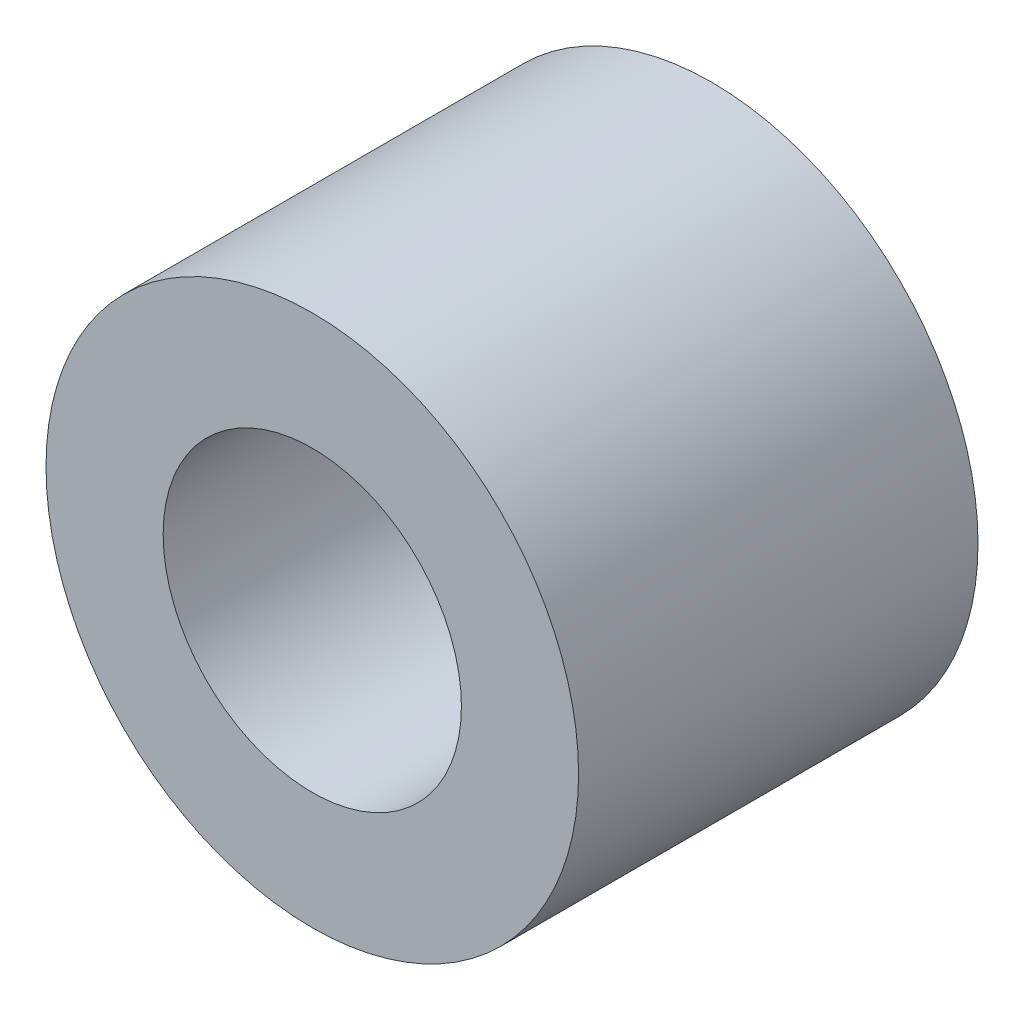
SolidWorks part; units mm, degrees
ref_plane "Front Plane" through (0, 0, 0) normal (0, 0, 1) x (1, 0, 0)
ref_plane "Top Plane" through (0, 0, 0) normal (0, 1, 0) x (1, 0, 0)
ref_plane "Right Plane" through (0, 0, 0) normal (1, 0, 0) x (0, 0, -1)
sketch "Sketch1" plane through (0, 0, 0) normal (0, 0, 1) x (1, 0, 0)
  circle A0 centre (0, 0) radius 3.175
  circle A1 centre (0, 0) radius 1.778
  dimension "OD" = 6.35
  dimension "ID" = 3.556
extrude "Extrude1" add sketch "Sketch1" along normal mid plane 4.7625
sketch "Sketch2" plane through (0, 0, 0) normal (1, 0, 0) x (0, 0, -1)
  line L0 (-2.3813, -1.778) -> (2.3812, -1.778) construction
  line L3 (2.3812, 1.778) -> (-2.3813, 1.778) construction
  line L5 (-2.3813, -1.778) -> (2.3812, -1.778)
  line L6 (2.3812, 1.778) -> (-2.3813, 1.778)
sketch "Sketch4" plane through (0, 0, 2.3813) normal (0, 0, 1) x (1, 0, 0)
  line L0 (0, 0) -> (-1.2572, 1.2572)
  line L1 (0, -1.7463) -> (0, 1.7463) construction
  circle A0 centre (0, 0) radius 1.778 construction
  dimension "D1" = 45
